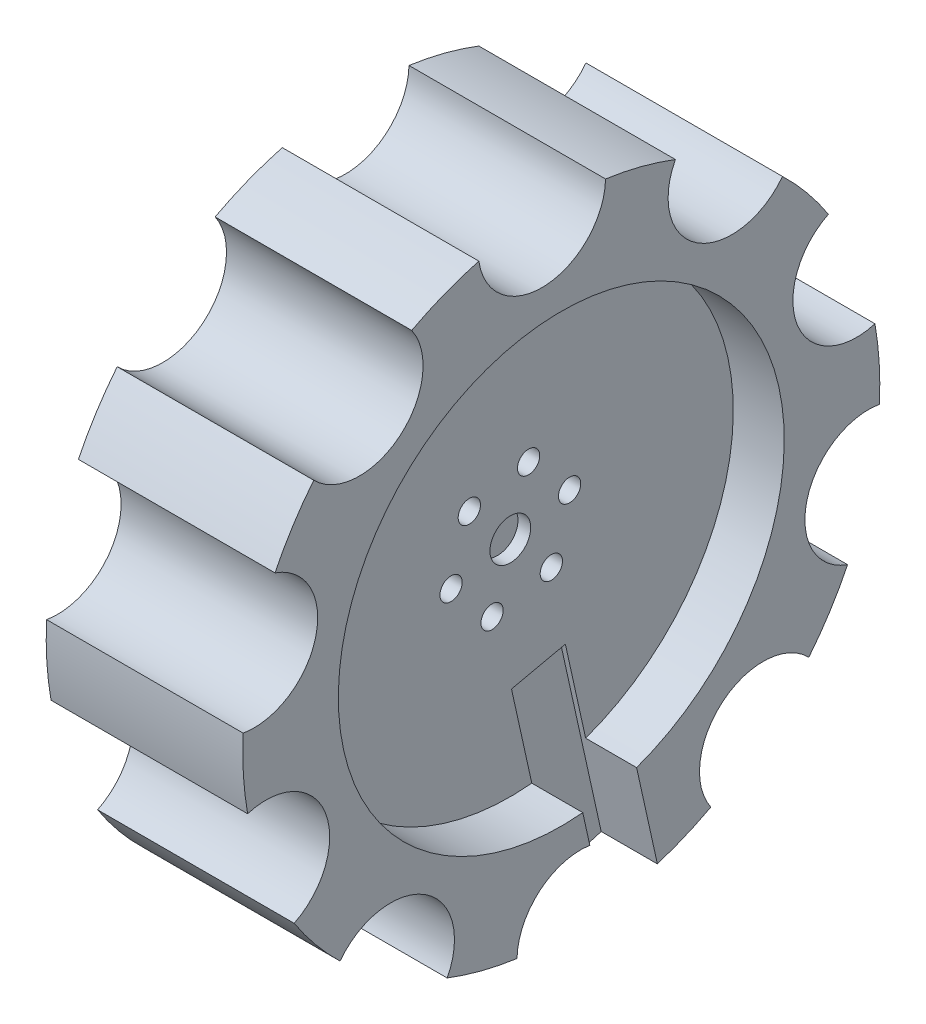
SolidWorks part; units mm, degrees
ref_plane "Front Plane" through (0, 0, 0) normal (0, 0, 1) x (1, 0, 0)
ref_plane "Top Plane" through (0, 0, 0) normal (0, 1, 0) x (1, 0, 0)
ref_plane "Right Plane" through (0, 0, 0) normal (1, 0, 0) x (0, 0, -1)
sketch "Sketch1" plane through (0, 0, 0) normal (1, 0, 0) x (0, 0, -1)
  circle A0 centre (0, 0) radius 50
extrude "Boss-Extrude1" add sketch "Sketch1" along normal blind 30.86
ref_axis "WheelAxis" through (0, 0, 0) along (1, 0, 0)
ref_point "Point1"
ref_point "Point2"
sketch "Sketch2" plane through (30.86, 0, 0) normal (1, 0, 0) x (0, 0, -1)
  circle A0 centre (0, 0) radius 35
extrude "Cut-Extrude1" cut sketch "Sketch2" against normal blind 8
sketch "Sketch3" plane through (0, 0, 0) normal (-1, 0, 0) x (0, 0, 1)
  circle A0 centre (0, 0) radius 29.8357
sketch "Sketch5" plane through (0, 0, 0) normal (-1, 0, 0) x (0, 0, 1)
  line L1 (-2.8683, 9.0881) -> (-9.3047, 2.0601) construction
  line L2 (-9.3047, 2.0601) -> (-6.4364, -7.0281) construction
  line L3 (-6.4364, -7.0281) -> (2.8683, -9.0881) construction
  line L4 (2.8683, -9.0881) -> (9.3047, -2.0601) construction
  line L5 (9.3047, -2.0601) -> (6.4364, 7.0281) construction
  line L6 (6.4364, 7.0281) -> (-2.8683, 9.0881) construction
  circle A0 centre (0, 0) radius 9.53 construction
  circle A1 centre (0, 0) radius 8.2532 construction
  circle A2 centre (2.8683, -9.0881) radius 1.75
  circle A3 centre (-6.4364, -7.0281) radius 1.75
  circle A4 centre (-9.3047, 2.0601) radius 1.75
  circle A5 centre (-2.8683, 9.0881) radius 1.75
  circle A6 centre (6.4364, 7.0281) radius 1.75
  circle A7 centre (9.3047, -2.0601) radius 1.75
ref_axis "ReferenceAxisForOrientation" through (0, -2.0601, 9.3047) along (0, 0.2162, -0.9764)
ref_plane "Plane1" through (0, 0, 0) normal (0, 0.9764, 0.2162) x (1, 0, 0)
sketch "Sketch10" plane through (0, 0, 0) normal (0, 0.9764, 0.2162) x (1, 0, 0)
  line L1 (22.0394, 4.422) -> (32.0581, 4.422)
  line L2 (22.0394, 4.422) -> (22.0394, -4.2399)
  line L3 (22.0394, -4.2399) -> (32.0581, -4.2399)
  line L4 (32.0581, 4.422) -> (32.0581, -4.2399)
extrude "Cut-Extrude4" cut sketch "Sketch10" against normal blind 60 from offset 20 offset against normal yes
ref_point "Point5"
sketch "Sketch12" plane through (22.86, 0, 0) normal (1, 0, 0) x (0, 0, -1)
  circle A0 centre (0, 0) radius 3.2
extrude "Cut-Extrude5" cut sketch "Sketch12" against normal blind 2
extrude "Cut-Extrude3" cut sketch "Sketch5" against normal blind 30
sketch "Sketch8" plane through (0, 0, 0) normal (-1, 0, 0) x (0, 0, 1)
  circle A0 centre (-2.8683, 9.0881) radius 4
  circle A1 centre (6.4364, 7.0281) radius 4
  circle A2 centre (9.3047, -2.0601) radius 4
  circle A3 centre (2.8683, -9.0881) radius 4
  circle A4 centre (-6.4364, -7.0281) radius 4
  circle A5 centre (-9.3047, 2.0601) radius 4
extrude "Cut-Extrude6" cut sketch "Sketch8" against normal blind 10
sketch "Sketch13" plane through (0, 0, 0) normal (-1, 0, 0) x (0, 0, 1)
  line L1 (-48.2406, -12.4708) -> (-31.6973, -38.4442) construction
  line L2 (-31.6973, -38.4442) -> (-3.0467, -49.7332) construction
  line L3 (-3.0467, -49.7332) -> (26.7676, -42.0258) construction
  line L4 (26.7676, -42.0258) -> (46.3576, -18.266) construction
  line L5 (46.3576, -18.266) -> (48.2406, 12.4708) construction
  line L6 (48.2406, 12.4708) -> (31.6973, 38.4442) construction
  line L7 (31.6973, 38.4442) -> (3.0467, 49.7332) construction
  line L8 (3.0467, 49.7332) -> (-26.7676, 42.0258) construction
  line L9 (-26.7676, 42.0258) -> (-46.3576, 18.266) construction
  line L10 (-46.3576, 18.266) -> (-48.2406, -12.4708) construction
  circle A0 centre (0, 0) radius 47.3878 construction
  circle A1 centre (48.2406, 12.4708) radius 10
  circle A2 centre (46.3576, -18.266) radius 10
  circle A3 centre (26.7676, -42.0258) radius 10
  circle A4 centre (-3.0467, -49.7332) radius 10
  circle A5 centre (-31.6973, -38.4442) radius 10
  circle A6 centre (-48.2406, -12.4708) radius 10
  circle A7 centre (-46.3576, 18.266) radius 10
  circle A8 centre (-26.7676, 42.0258) radius 10
  circle A9 centre (3.0467, 49.7332) radius 10
  circle A10 centre (31.6973, 38.4442) radius 10
  point P23 (-17.372, -44.0887)
extrude "Cut-Extrude8" cut sketch "Sketch13" against normal blind 40
